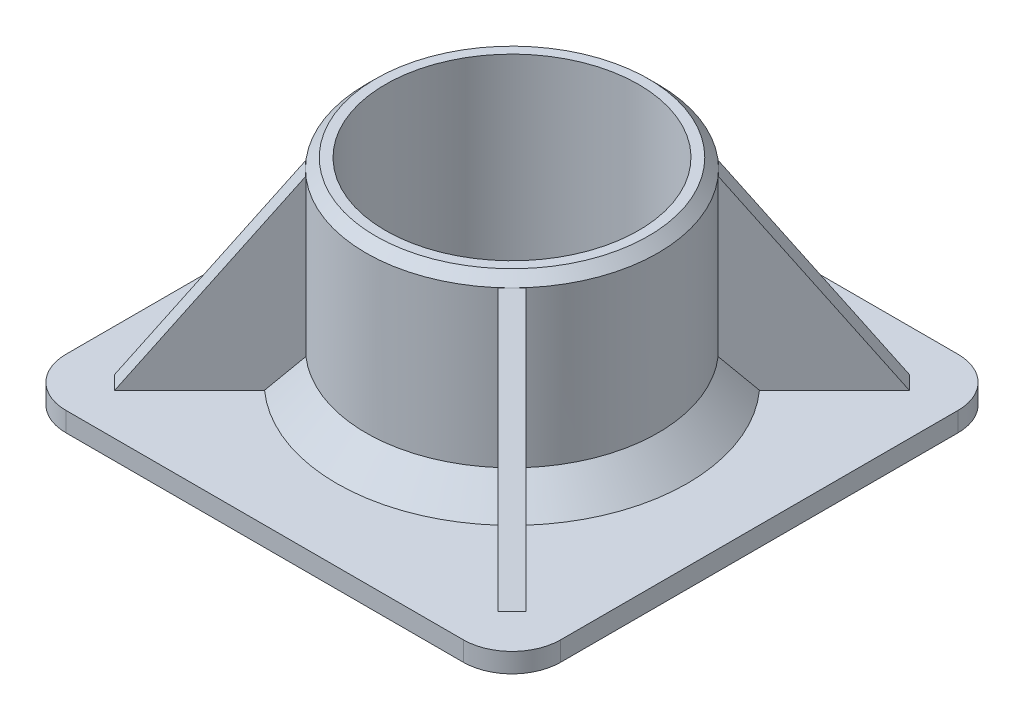
SolidWorks part; units mm, degrees
ref_plane "Front Plane" through (0, 0, 0) normal (0, 0, 1) x (1, 0, 0)
ref_plane "Top Plane" through (0, 0, 0) normal (0, 1, 0) x (1, 0, 0)
ref_plane "Right Plane" through (0, 0, 0) normal (1, 0, 0) x (0, 0, -1)
sketch "Sketch1" plane through (0, 0, 0) normal (0, 1, 0) x (1, 0, 0)
  line L1 (-25.4, 25.4) -> (25.4, 25.4)
  line L2 (-25.4, 25.4) -> (-25.4, -25.4)
  line L3 (-25.4, -25.4) -> (25.4, -25.4)
  line L4 (25.4, 25.4) -> (25.4, -25.4)
  line L5 (-25.4, 25.4) -> (25.4, -25.4) construction
  line L6 (-25.4, -25.4) -> (25.4, 25.4) construction
  point P0 (0, 0)
  dimension "D1" = 50.8
  dimension "D2" = 50.8
extrude "Boss-Extrude1" add sketch "Sketch1" along normal blind 2
sketch "Sketch2" plane through (0, 2, 0) normal (0, 1, 0) x (1, 0, 0)
  circle A0 centre (0, 0) radius 13
  circle A1 centre (0, 0) radius 15
  dimension "D1" = 26
  dimension "D2" = 2
extrude "Boss-Extrude2" add sketch "Sketch2" along normal blind 20
chamfer "Chamfer1" distance 1 angle 45 1 edges at (0, 22, 15)
fillet "Fillet1" radius 5 4 edges at (25.4, 1, -25.4) (-25.4, 1, -25.4) (25.4, 1, 25.4) (-25.4, 1, 25.4)
sketch "Sketch3" plane through (0, 2, 0) normal (0, 1, 0) x (1, 0, 0)
  line L0 (20.4, -20.4) -> (-20.4, 20.4) construction
  line L1 (-20.4, -20.4) -> (20.4, 20.4) construction
sketch "Sketch4" plane through (0, 0, 0) normal (1, 0, 0) x (0, 0, -1)
  line L0 (0, 0) -> (0, 25.646) construction
ref_plane "Plane1" through (0, 0, 0) normal (0.7071, 0, -0.7071) x (-0.7071, 0, -0.7071)
ref_plane "Plane2" through (0, 0, 0) normal (0.7071, 0, 0.7071) x (0.7071, 0, -0.7071)
sketch "Sketch5" plane through (0, 0, 0) normal (0.7071, 0, -0.7071) x (-0.7071, 0, -0.7071)
  line L0 (-15, 21) -> (-28.85, 2)
  line L1 (-28.85, 2) -> (-14.2119, 2)
  line L2 (-14.2119, 2) -> (-14.2119, 20.9288)
  line L3 (15, 21) -> (28.85, 2)
  line L4 (28.85, 2) -> (14.2363, 2)
  line L5 (14.2363, 2) -> (14.2363, 20.9288)
  line L6 (-15, 21) -> (-14.2119, 20.9288)
  line L7 (-15, 21) -> (-15, 2) construction
  line L8 (15, 21) -> (14.2363, 20.9288)
extrude "Boss-Extrude4" add sketch "Sketch5" along normal blind 1 and the other way blind 1
sketch "Sketch6" plane through (0, 0, 0) normal (0.7071, 0, 0.7071) x (0.7071, 0, -0.7071)
  line L0 (-15, 21) -> (-28.85, 2)
  line L1 (-28.85, 2) -> (-14.1713, 2)
  line L2 (-14.1713, 2) -> (-14.1713, 20.3959)
  line L3 (15, 21) -> (28.85, 2)
  line L4 (28.85, 2) -> (14.1522, 2)
  line L5 (14.1522, 2) -> (14.1522, 20.382)
  line L6 (-15, 21) -> (-14.1713, 20.3959)
  line L7 (-14, 22) -> (-15, 21) construction
  line L8 (15, 21) -> (14.1522, 20.382)
extrude "Boss-Extrude5" add sketch "Sketch6" along normal blind 1 and the other way blind 1
sketch "Sketch7" plane through (0, 2, 0) normal (0, 1, 0) x (1, 0, 0)
  circle A0 centre (-0.1999, -0.2259) radius 6.35
  dimension "D1" = 12.7
extrude "Cut-Extrude1" cut sketch "Sketch7" against normal blind 11
chamfer "Chamfer2" distance 3 angle 45 4 edges at (0, 2, -15) (15, 2, 0) (0, 2, 15) (-15, 2, 0)
